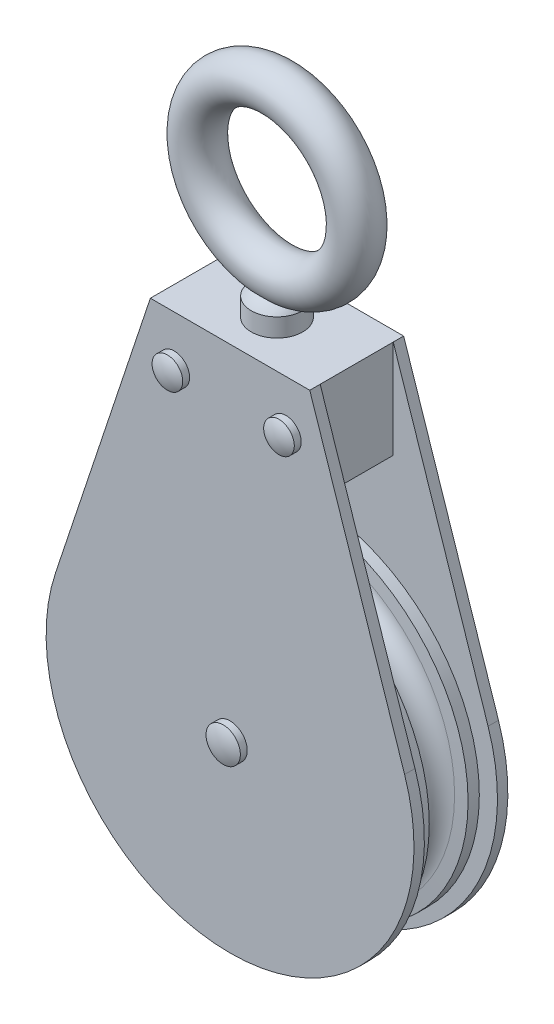
SolidWorks part; units mm, degrees
ref_plane "Front Plane" through (0, 0, 0) normal (0, 0, 1) x (1, 0, 0)
ref_plane "Top Plane" through (0, 0, 0) normal (0, 1, 0) x (1, 0, 0)
ref_plane "Right Plane" through (0, 0, 0) normal (1, 0, 0) x (0, 0, -1)
sketch "Sketch1" plane through (0, 0, 0) normal (0, 0, 1) x (1, 0, 0)
  line L0 (0, -47.625) -> (0, 146.05) construction
  line L2 (-26.1937, 119.8562) -> (26.1937, 119.8562) construction
  line L5 (-20.6375, 88.9) -> (20.6375, 88.9)
  line L10 (0, 146.05) -> (19.05, 146.05) construction
  line L12 (15.0812, 119.8562) -> (26.1937, 119.8562) construction
  circle A0 centre (0, 0) radius 47.625 construction
  circle A1 centre (0, 119.8562) radius 15.0813 construction
  circle A13 centre (0, 119.8562) radius 26.1938
  circle A16 centre (0, 0) radius 44.45
  point P15 (0, 44.45)
  point P16 (0, 88.9)
  point P20 (20.6375, 119.8562)
  point P22 (0, 134.9375)
  point P25 (0, 119.8562)
  dimension "O" = 95.25
  dimension "D" = 52.3875
  dimension "Overall Height" = 193.675
  dimension "G" = 136.525
  dimension "D1" = 41.275
sketch "Sketch2" plane through (0, 0, 0) normal (0, 0, 1) x (1, 0, 0)
  line L0 (-20.6375, 88.9) -> (20.6375, 88.9)
  line L1 (-20.6375, 88.9) -> (-45.1938, 15.022)
  line L2 (20.6375, 88.9) -> (45.1938, 15.022)
  circle A2 centre (0, 0) radius 47.625 construction
  arc A3 (-45.1938, 15.022) -> (45.1938, 15.022) centre (0, 0) ccw
sketch "Sketch3" plane through (0, 0, 0) normal (1, 0, 0) x (0, 0, -1)
  line L0 (-7.9375, 44.45) -> (-7.9375, 0)
  line L1 (-7.9375, 0) -> (7.9375, 0) construction
  line L2 (7.9375, 0) -> (7.9375, 44.45)
  line L3 (7.9375, 44.45) -> (5.0251, 44.45)
  line L4 (5.0251, 44.45) -> (4.7444, 41.2409)
  line L5 (-7.9375, 44.45) -> (-5.0251, 44.45)
  line L6 (-4.7444, 41.2409) -> (-5.0251, 44.45)
  line L8 (0, 44.45) -> (0, -44.45) construction
  line L9 (-7.9375, 0) -> (7.9375, 0)
  line L10 (7.9375, 0) -> (14.6481, 0) construction
  line L11 (0, -47.625) -> (0, 146.05) construction
  arc A0 (4.7444, 41.2409) -> (-4.7444, 41.2409) centre (0, 41.656) cw
  circle A1 centre (0, 41.656) radius 4.7625 construction
  circle A2 centre (0, -41.656) radius 4.7625 construction
  circle A3 centre (0, 140.4937) radius 5.5562 construction
  dimension "Rope Dia" = 9.525
  dimension "D1" = 73.787
  dimension "D4" = 5
  dimension "Pulley Width" = 15.875
revolve "Revolve1" add sketch "Sketch3" angle 360 about L1
ref_plane "Plane1" through (0, 0, 9.4615) normal (0, 0, 1) x (1, 0, 0)
ref_plane "Plane2" through (0, 119.8562, 0) normal (0, 1, 0) x (-1, 0, 0)
sketch "Sketch10" plane through (0, 119.8562, 0) normal (0, 1, 0) x (-1, 0, 0)
  circle A0 centre (-20.6375, 0) radius 5.5562
  dimension "D1" = 11.1125
sketch "Sketch11" plane through (0, 0, 0) normal (0, 0, 1) x (1, 0, 0)
  line L1 (-26.1937, 119.8562) -> (26.1937, 119.8562) construction
  arc A0 (20.6375, 119.8562) -> (-20.6375, 119.8562) centre (0, 119.8562) ccw
  point P4 (-20.6375, 119.8562)
sweep "Sweep2" add profiles "Sketch10" path "Sketch11"
mirror "Mirror7" about plane through (20.6375, 119.8562, 0) normal (0, 1, 0) of bodies 118
sketch "Sketch12" plane through (0, 0, 0) normal (0, 0, 1) x (1, 0, 0)
  line L0 (-6.6675, 88.9) -> (6.6675, 88.9)
  line L1 (6.6675, 88.9) -> (6.6675, 93.6625)
  line L2 (-6.6675, 88.9) -> (-6.6675, 93.6625)
  line L3 (0, -47.625) -> (0, 146.05) construction
  line L5 (0, 93.6625) -> (0, 104.775) construction
  circle A1 centre (0, 119.8562) radius 26.1938 construction
  circle A2 centre (0, 119.8562) radius 15.0813 construction
  arc A3 (6.6675, 93.6625) -> (-6.6675, 93.6625) centre (0, 89.5138) ccw
  point P8 (0, 97.3667)
  point P10 (0, 93.6625)
  point P17 (0, 99.2187)
  dimension "D1" = 13.335
  dimension "D2" = 11.1125
  dimension "D4" = 3.7042
sketch "Sketch14" plane through (0, 0, 0) normal (0, 0, 1) x (1, 0, 0)
  line L0 (6.6675, 88.9) -> (6.6675, 93.6625) construction
  line L1 (-20.6375, 88.9) -> (20.6375, 88.9) construction
  line L2 (6.6675, 88.9) -> (6.6675, 93.6625)
  line L3 (0, 88.9) -> (6.6675, 88.9)
  line L4 (0, 53.1812) -> (0, 88.9) construction
  line L5 (0, 97.3667) -> (0, 88.9)
  arc A1 (6.6675, 93.6625) -> (-6.6675, 93.6625) centre (0, 89.5138) ccw construction
  arc A2 (6.6675, 93.6625) -> (0, 97.3667) centre (0, 89.5138) ccw
revolve "Revolve2" add sketch "Sketch14" angle 360 about L4
sketch "Sketch4" plane through (0, 0, 9.4615) normal (0, 0, 1) x (1, 0, 0)
  line L2 (-20.6375, 88.9) -> (20.6375, 88.9)
  line L3 (20.6375, 88.9) -> (-20.6375, 88.9)
  line L4 (45.1938, 15.022) -> (20.6375, 88.9)
  line L5 (-20.6375, 88.9) -> (-45.1938, 15.022)
  line L7 (45.1938, 15.022) -> (20.6375, 88.9)
  line L8 (-20.6375, 88.9) -> (-45.1938, 15.022)
  arc A1 (-45.1938, 15.022) -> (45.1938, 15.022) centre (0, 0) ccw
  arc A2 (-45.1938, 15.022) -> (45.1938, 15.022) centre (0, 0) ccw
  dimension "D1" = 0
extrude "Boss-Extrude1" add sketch "Sketch4" along normal blind 2.6924 separate body
sketch "Sketch5" plane through (0, 0, 9.4615) normal (0, 0, -1) x (-1, 0, 0)
  line L1 (-20.6375, 88.9) -> (20.6375, 88.9)
  line L2 (-20.6375, 88.9) -> (-20.6375, 63.5)
  line L3 (-20.6375, 63.5) -> (20.6375, 63.5)
  line L4 (20.6375, 88.9) -> (20.6375, 63.5)
  dimension "D1" = 25.4
extrude "Boss-Extrude2" add sketch "Sketch5" along normal up to surface (9.4615 mm away) up to plane "Front Plane"
mirror "Mirror1" about plane through (0, 0, 0) normal (0, 0, 1) of bodies 103 104
sketch "Sketch6" plane through (0, 0, 12.1539) normal (0, 0, 1) x (1, 0, 0)
  line L0 (-14.4462, 76.2) -> (14.4462, 76.2) construction
  line L1 (0, 76.2) -> (0, 0) construction
  line L2 (20.6375, 76.2) -> (14.4462, 76.2) construction
  line L4 (-20.6375, 76.2) -> (-14.4462, 76.2) construction
  line L6 (-20.6375, 63.5) -> (-20.6375, 88.9) construction
  line L7 (20.6375, 88.9) -> (20.6375, 63.5) construction
  circle A0 centre (0, 0) radius 4.445
  circle A1 centre (-14.4462, 76.2) radius 3.9687
  circle A2 centre (14.4462, 76.2) radius 3.9688
  dimension "D1" = 7.9375
  dimension "D3" = 8.89
  dimension "D2" = 28.8925
extrude "Boss-Extrude3" add sketch "Sketch6" along normal blind 1.778
dome "Dome1" faces to dome 1 distance 1.016 reverse direction no elliptical dome no face at (-10.4775, 76.2, 13.9319) parameters "D1"=1.016
dome "Dome3" faces to dome 1 distance 1.016 reverse direction no elliptical dome no face at (18.415, 76.2, 13.9319) parameters "D1"=1.016
dome "Dome4" faces to dome 1 distance 1.016 reverse direction no elliptical dome no face at (4.445, 0, 13.9319) parameters "D1"=1.016
sketch "Sketch8" plane through (0, 0, -12.1539) normal (0, 0, -1) x (-1, 0, 0)
  circle A0 centre (-14.4462, 76.2) radius 5.5562
  circle A1 centre (14.4462, 76.2) radius 5.5562
  circle A2 centre (0, 0) radius 7.9375
  dimension "D1" = 15.875
  dimension "D2" = 11.1125
extrude "Boss-Extrude4" add sketch "Sketch8" along normal blind 1.778
dome "Dome5" faces to dome 1 distance 2.54 reverse direction no elliptical dome no face at (8.89, 76.2, -13.9319) parameters "D1"=2.54
dome "Dome6" faces to dome 1 distance 2.54 reverse direction no elliptical dome no face at (-20.0025, 76.2, -13.9319) parameters "D1"=2.54
dome "Dome7" faces to dome 1 distance 3.9624 reverse direction no elliptical dome no face at (-7.9375, 0, -13.9319) parameters "D1"=3.9624
sketch "Sketch9" plane through (0, 0, 12.1539) normal (0, 0, 1) x (1, 0, 0)
  circle A0 centre (0, 0) radius 3.575
  dimension "D1" = 7.1501
extrude "Boss-Extrude5" add sketch "Sketch9" against normal up to surface (24.3078 mm away) up to face at (-20.0025, 76.2, -12.1539)
combine bodies "Combine1" operation type add bodies to combine 107 120
sketch "Sketch15" plane through (0, 63.5, 0) normal (0, -1, 0) x (1, 0, 0)
  circle A0 centre (0, 0) radius 6.6675
  circle A1 centre (0, 0) radius 6.6675 construction
extrude "Boss-Extrude6" add sketch "Sketch15" along normal blind 4.064
fillet "Fillet1" radius 2.032 1 edges at (0, 59.436, -6.6675)
equation "\"D1@Sketch3\" = \"Pulley Dia@Sketch1\"*.83"
equation "\"D2@Sketch6\" = \"D1@Sketch1\"*.7"
equation "\"D1@Sketch12\" = \"D1@Sketch10\"*1.2"
equation "\"D4@Sketch12\" = \"D2@Sketch12\"/3"
